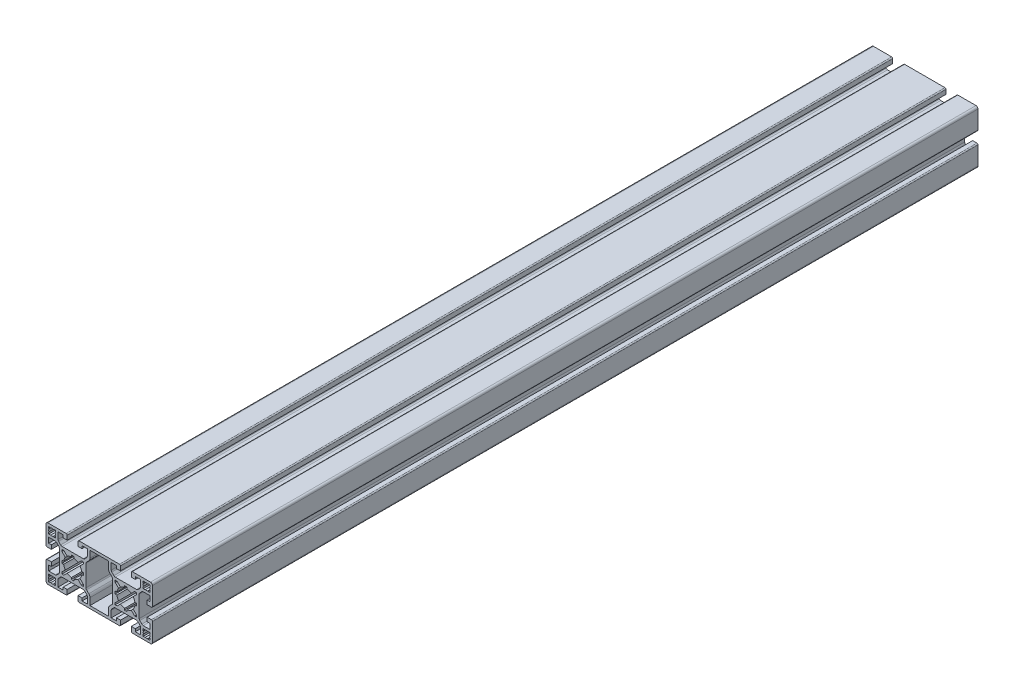
SolidWorks part; units mm, degrees
material "6063-T5"
ref_plane "Plano frontal" through (0, 0, 0) normal (0, 0, 1) x (1, 0, 0)
ref_plane "Plano superior" through (0, 0, 0) normal (0, 1, 0) x (1, 0, 0)
ref_plane "Plano direito" through (0, 0, 0) normal (1, 0, 0) x (0, 0, -1)
sketch "Esboço1" plane through (0, 0, 0) normal (0, 0, 1) x (1, 0, 0)
  line L0 (-33, 18) -> (-33, 16.5858)
  line L1 (-38.5, 20) -> (-24.85, 20)
  line L2 (-40, 18.5) -> (-40, 4.85)
  line L3 (-31, 18) -> (-27.05, 18)
  line L4 (-33, 18) -> (-34.4142, 18)
  line L5 (-30.5607, 11.9749) -> (-29.0251, 10.4393)
  line L6 (-27.9645, 10) -> (-12.0355, 10)
  line L7 (-34.4142, 18) -> (-34.5869, 17.8273)
  line L8 (-36.5858, 18) -> (-36.4131, 17.8273)
  line L9 (-33, 13) -> (-34.4142, 13)
  line L10 (-33, 13) -> (-33, 14.4142)
  line L11 (-36, 7.05) -> (-36, 4.05)
  line L12 (-33, 14.4142) -> (-33.1727, 14.5869)
  line L13 (-28, 6.5858) -> (-25.4989, 4.0847)
  line L14 (-21, 8) -> (-19, 8)
  line L15 (-21, 8) -> (-21, 6.7766)
  line L16 (-33, 16.5858) -> (-33.1727, 16.4131)
  line L17 (-28, 8) -> (-28, 6.5858)
  line L18 (-38, 13) -> (-38, 14.4142)
  line L19 (-38, 13) -> (-36.5858, 13)
  line L20 (-36.5858, 13) -> (-36.4131, 13.1727)
  line L21 (-34.4142, 13) -> (-34.5869, 13.1727)
  line L22 (-30, 7.9645) -> (-30, -7.9645)
  line L23 (-38, -11) -> (-38, -7.05)
  line L24 (-38, -14.4142) -> (-37.8273, -14.5869)
  line L25 (-7, 18) -> (-7, 12.8284)
  line L26 (-38, 18) -> (-36.5858, 18)
  line L27 (-38, 18) -> (-38, 16.5858)
  line L28 (-9.5607, 9.0251) -> (-7.8787, 10.7071)
  line L29 (-31.9749, -10.5607) -> (-30.4393, -9.0251)
  line L30 (-28, -1) -> (-26.7766, -1)
  line L31 (-9, -18) -> (-12.95, -18)
  line L32 (-24.05, 19.2) -> (-24.05, 16)
  line L33 (-9.4393, -11.9749) -> (-10.9749, -10.4393)
  line L34 (-38, 7.05) -> (-36, 7.05)
  line L35 (-19, -8) -> (-19, -6.7766)
  line L36 (-15.95, -19.2) -> (-15.95, -16)
  line L37 (-12.95, 16) -> (-15.95, 16)
  line L38 (-38, 11) -> (-33.0355, 11)
  line L39 (-31, 18) -> (-31, 13.0355)
  line L40 (-12, -6.5858) -> (-14.5011, -4.0847)
  line L41 (-13.4142, 8) -> (-15.9153, 5.4989)
  line L42 (-12, -8) -> (-12, -6.5858)
  line L43 (-12, 1) -> (-13.2234, 1)
  line L44 (-27.05, 18) -> (-27.05, 16)
  line L45 (-9, -18) -> (-9, -13.0355)
  line L46 (-28, 8) -> (-26.5858, 8)
  line L47 (-26.5858, 8) -> (-24.0847, 5.4989)
  line L48 (-27.05, 16) -> (-24.05, 16)
  line L49 (-12.95, -18) -> (-12.95, -16)
  line L50 (-38, -16.5858) -> (-37.8273, -16.4131)
  line L51 (-12, 8) -> (-13.4142, 8)
  line L52 (-39.2, -4.05) -> (-36, -4.05)
  line L53 (-12, -8) -> (-13.4142, -8)
  line L54 (-27.05, -16) -> (-24.05, -16)
  line L55 (-26.5858, -8) -> (-24.0847, -5.4989)
  line L56 (-28, -8) -> (-26.5858, -8)
  line L57 (-39.2, 4.05) -> (-36, 4.05)
  line L58 (-27.05, -18) -> (-27.05, -16)
  line L59 (-38, 16.5858) -> (-37.8273, 16.4131)
  line L60 (-12, -1) -> (-13.2234, -1)
  line L61 (-12.95, 18) -> (-12.95, 16)
  line L62 (-9, 18) -> (-9, 13.0355)
  line L63 (-13.4142, -8) -> (-15.9153, -5.4989)
  line L64 (-31, -18) -> (-31, -13.0355)
  line L65 (-12, 8) -> (-12, 6.5858)
  line L66 (-12, 6.5858) -> (-14.5011, 4.0847)
  line L67 (-38, -11) -> (-33.0355, -11)
  line L68 (-12.95, -16) -> (-15.95, -16)
  line L69 (-38, -7.05) -> (-36, -7.05)
  line L70 (-15.95, 19.2) -> (-15.95, 16)
  line L71 (-24.05, -19.2) -> (-24.05, -16)
  line L72 (-9.5607, -9.0251) -> (-7.8787, -10.7071)
  line L73 (-19, 8) -> (-19, 6.7766)
  line L74 (-38, -18) -> (-38, -16.5858)
  line L75 (-9.4393, 11.9749) -> (-10.9749, 10.4393)
  line L76 (-38, -18) -> (-36.5858, -18)
  line L77 (-9, 18) -> (-12.95, 18)
  line L78 (-7, -18) -> (-7, -12.8284)
  line L79 (-34.4142, -13) -> (-34.5869, -13.1727)
  line L80 (-36.5858, -13) -> (-36.4131, -13.1727)
  line L81 (-38, -13) -> (-36.5858, -13)
  line L82 (-38, -13) -> (-38, -14.4142)
  line L83 (-28, -8) -> (-28, -6.5858)
  line L84 (-33, -16.5858) -> (-33.1727, -16.4131)
  line L85 (-21, -8) -> (-21, -6.7766)
  line L86 (-21, -8) -> (-19, -8)
  line L87 (-28, -6.5858) -> (-25.4989, -4.0847)
  line L88 (-33, -14.4142) -> (-33.1727, -14.5869)
  line L89 (-36, -7.05) -> (-36, -4.05)
  line L90 (-33, -13) -> (-33, -14.4142)
  line L91 (-33, -13) -> (-34.4142, -13)
  line L92 (-36.5858, -18) -> (-36.4131, -17.8273)
  line L93 (-34.4142, -18) -> (-34.5869, -17.8273)
  line L94 (-27.9645, -10) -> (-12.0355, -10)
  line L95 (-30.5607, -11.9749) -> (-29.0251, -10.4393)
  line L96 (-33, -18) -> (-34.4142, -18)
  line L97 (-31, -18) -> (-27.05, -18)
  line L98 (-40, -18.5) -> (-40, -4.85)
  line L99 (-38.5, -20) -> (-24.85, -20)
  line L100 (-33, -18) -> (-33, -16.5858)
  line L101 (-28, 1) -> (-28, -1)
  line L102 (-12, -1) -> (-12, 1)
  line L103 (-10, 7.9645) -> (-10, -7.9645)
  line L104 (-15.15, 20) -> (15.15, 20)
  line L105 (-15.15, -20) -> (15.15, -20)
  line L108 (0, 25.8211) -> (0, -27.4656) construction
  line L109 (38, 11) -> (38, 7.05)
  line L110 (38, 14.4142) -> (37.8273, 14.5869)
  line L111 (-28, 1) -> (-26.7766, 1)
  line L112 (31.9749, 10.5607) -> (30.4393, 9.0251)
  line L113 (28, 1) -> (26.7766, 1)
  line L118 (10, 7.9645) -> (10, -7.9645)
  line L119 (12, -1) -> (12, 1)
  line L120 (-31.9749, 10.5607) -> (-30.4393, 9.0251)
  line L121 (28, 1) -> (28, -1)
  line L122 (33, -18) -> (33, -16.5858)
  line L123 (-38, 14.4142) -> (-37.8273, 14.5869)
  line L124 (38.5, -20) -> (24.85, -20)
  line L125 (40, -18.5) -> (40, -4.85)
  line L126 (31, -18) -> (27.05, -18)
  line L127 (33, -18) -> (34.4142, -18)
  line L128 (-38, 11) -> (-38, 7.05)
  line L129 (30.5607, -11.9749) -> (29.0251, -10.4393)
  line L130 (27.9645, -10) -> (12.0355, -10)
  line L131 (34.4142, -18) -> (34.5869, -17.8273)
  line L132 (36.5858, -18) -> (36.4131, -17.8273)
  line L133 (33, -13) -> (34.4142, -13)
  line L134 (33, -13) -> (33, -14.4142)
  line L135 (36, -7.05) -> (36, -4.05)
  line L136 (33, -14.4142) -> (33.1727, -14.5869)
  line L137 (28, -6.5858) -> (25.4989, -4.0847)
  line L138 (21, -8) -> (19, -8)
  line L139 (21, -8) -> (21, -6.7766)
  line L140 (33, -16.5858) -> (33.1727, -16.4131)
  line L141 (28, -8) -> (28, -6.5858)
  line L142 (38, -13) -> (38, -14.4142)
  line L143 (38, -13) -> (36.5858, -13)
  line L144 (36.5858, -13) -> (36.4131, -13.1727)
  line L145 (34.4142, -13) -> (34.5869, -13.1727)
  line L146 (7, -18) -> (7, -12.8284)
  line L147 (9, 18) -> (12.95, 18)
  line L148 (38, -18) -> (36.5858, -18)
  line L149 (9.4393, 11.9749) -> (10.9749, 10.4393)
  line L150 (38, -18) -> (38, -16.5858)
  line L151 (19, 8) -> (19, 6.7766)
  line L152 (9.5607, -9.0251) -> (7.8787, -10.7071)
  line L153 (24.05, -19.2) -> (24.05, -16)
  line L154 (15.95, 19.2) -> (15.95, 16)
  line L155 (38, -7.05) -> (36, -7.05)
  line L156 (12.95, -16) -> (15.95, -16)
  line L157 (38, -11) -> (33.0355, -11)
  line L158 (12, 6.5858) -> (14.5011, 4.0847)
  line L159 (12, 8) -> (12, 6.5858)
  line L160 (31, -18) -> (31, -13.0355)
  line L161 (13.4142, -8) -> (15.9153, -5.4989)
  line L162 (9, 18) -> (9, 13.0355)
  line L163 (12.95, 18) -> (12.95, 16)
  line L164 (12, -1) -> (13.2234, -1)
  line L165 (38, 16.5858) -> (37.8273, 16.4131)
  line L166 (27.05, -18) -> (27.05, -16)
  line L167 (39.2, 4.05) -> (36, 4.05)
  line L168 (28, -8) -> (26.5858, -8)
  line L169 (26.5858, -8) -> (24.0847, -5.4989)
  line L170 (27.05, -16) -> (24.05, -16)
  line L171 (12, -8) -> (13.4142, -8)
  line L172 (39.2, -4.05) -> (36, -4.05)
  line L173 (-1.5, 20) -> (-15.15, 20) [skipped]
  line L174 (0, 18.5) -> (0, 4.85) [skipped]
  line L175 (12, 8) -> (13.4142, 8)
  line L176 (0, -18.5) -> (0, -4.85) [skipped]
  line L177 (-0.8, 4.05) -> (-4, 4.05) [skipped]
  line L178 (-0.8, -4.05) -> (-4, -4.05) [skipped]
  line L179 (-1.5, -20) -> (-15.15, -20) [skipped]
  line L180 (38, -16.5858) -> (37.8273, -16.4131)
  line L181 (-2, 11) -> (-6.9645, 11) [skipped]
  line L182 (-7, 13) -> (-5.5858, 13) [skipped]
  line L183 (-7, 18) -> (-5.5858, 18) [skipped]
  line L184 (-2, 18) -> (-3.4142, 18) [skipped]
  line L185 (-2, 18) -> (-2, 16.5858) [skipped]
  line L186 (-2, 13) -> (-2, 14.4142) [skipped]
  line L187 (-2, 13) -> (-3.4142, 13) [skipped]
  line L188 (-2, 11) -> (-2, 7.05) [skipped]
  line L189 (-2, 7.05) -> (-4, 7.05) [skipped]
  line L190 (-4, 7.05) -> (-4, 4.05) [skipped]
  line L191 (-7, 13) -> (-7, 14.4142) [skipped]
  line L192 (-5.5858, 13) -> (-5.4131, 13.1727) [skipped]
  line L193 (-2, 14.4142) -> (-2.1727, 14.5869) [skipped]
  line L194 (-2, 16.5858) -> (-2.1727, 16.4131) [skipped]
  line L195 (-3.4142, 13) -> (-3.5869, 13.1727) [skipped]
  line L196 (-7, 14.4142) -> (-6.8273, 14.5869) [skipped]
  line L197 (-3.4142, 18) -> (-3.5869, 17.8273) [skipped]
  line L198 (-5.5858, 18) -> (-5.4131, 17.8273) [skipped]
  line L199 (-7, 18) -> (-7, 16.5858) [skipped]
  line L200 (-7, 16.5858) -> (-6.8273, 16.4131) [skipped]
  line L201 (-8.0251, 10.5607) -> (-9.5607, 9.0251) [skipped]
  line L202 (-8.0251, -10.5607) -> (-9.5607, -9.0251) [skipped]
  line L203 (-2, -11) -> (-6.9645, -11) [skipped]
  line L204 (-2, -11) -> (-2, -7.05) [skipped]
  line L205 (-2, -7.05) -> (-4, -7.05) [skipped]
  line L206 (-4, -7.05) -> (-4, -4.05) [skipped]
  line L207 (-7, -18) -> (-7, -16.5858) [skipped]
  line L208 (-7, -18) -> (-5.5858, -18) [skipped]
  line L209 (-5.5858, -18) -> (-5.4131, -17.8273) [skipped]
  line L210 (-3.4142, -18) -> (-3.5869, -17.8273) [skipped]
  line L211 (-7, -13) -> (-5.5858, -13) [skipped]
  line L212 (-7, -13) -> (-7, -14.4142) [skipped]
  line L213 (-7, -14.4142) -> (-6.8273, -14.5869) [skipped]
  line L214 (-7, -16.5858) -> (-6.8273, -16.4131) [skipped]
  line L215 (-2, -13) -> (-2, -14.4142) [skipped]
  line L216 (-2, -13) -> (-3.4142, -13) [skipped]
  line L217 (-3.4142, -13) -> (-3.5869, -13.1727) [skipped]
  line L218 (-5.5858, -13) -> (-5.4131, -13.1727) [skipped]
  line L219 (-2, -18) -> (-3.4142, -18) [skipped]
  line L220 (-2, -18) -> (-2, -16.5858) [skipped]
  line L221 (-2, -16.5858) -> (-2.1727, -16.4131) [skipped]
  line L222 (-2, -14.4142) -> (-2.1727, -14.5869) [skipped]
  line L223 (12.95, -18) -> (12.95, -16)
  line L224 (-40, -18.5) -> (-40, -4.85) [skipped]
  line L225 (27.05, 16) -> (24.05, 16)
  line L226 (26.5858, 8) -> (24.0847, 5.4989)
  line L227 (28, 8) -> (26.5858, 8)
  line L228 (9, -18) -> (9, -13.0355)
  line L229 (27.05, 18) -> (27.05, 16)
  line L230 (12, 1) -> (13.2234, 1)
  line L231 (12, -8) -> (12, -6.5858)
  line L232 (13.4142, 8) -> (15.9153, 5.4989)
  line L233 (12, -6.5858) -> (14.5011, -4.0847)
  line L234 (31, 18) -> (31, 13.0355)
  line L235 (38, 11) -> (33.0355, 11)
  line L236 (12.95, 16) -> (15.95, 16)
  line L237 (15.95, -19.2) -> (15.95, -16)
  line L238 (19, -8) -> (19, -6.7766)
  line L239 (38, 7.05) -> (36, 7.05)
  line L240 (9.4393, -11.9749) -> (10.9749, -10.4393)
  line L241 (24.05, 19.2) -> (24.05, 16)
  line L242 (9, -18) -> (12.95, -18)
  line L243 (28, -1) -> (26.7766, -1)
  line L244 (31.9749, -10.5607) -> (30.4393, -9.0251)
  line L245 (9.5607, 9.0251) -> (7.8787, 10.7071)
  line L246 (38, 18) -> (38, 16.5858)
  line L247 (38, 18) -> (36.5858, 18)
  line L248 (7, 18) -> (7, 12.8284)
  line L249 (38, -14.4142) -> (37.8273, -14.5869)
  line L250 (38, -11) -> (38, -7.05)
  line L251 (30, 7.9645) -> (30, -7.9645)
  line L252 (34.4142, 13) -> (34.5869, 13.1727)
  line L253 (36.5858, 13) -> (36.4131, 13.1727)
  line L254 (38, 13) -> (36.5858, 13)
  line L255 (38, 13) -> (38, 14.4142)
  line L256 (28, 8) -> (28, 6.5858)
  line L257 (33, 16.5858) -> (33.1727, 16.4131)
  line L258 (21, 8) -> (21, 6.7766)
  line L259 (21, 8) -> (19, 8)
  line L260 (28, 6.5858) -> (25.4989, 4.0847)
  line L261 (33, 14.4142) -> (33.1727, 14.5869)
  line L262 (36, 7.05) -> (36, 4.05)
  line L263 (33, 13) -> (33, 14.4142)
  line L264 (33, 13) -> (34.4142, 13)
  line L265 (36.5858, 18) -> (36.4131, 17.8273)
  line L266 (34.4142, 18) -> (34.5869, 17.8273)
  line L267 (27.9645, 10) -> (12.0355, 10)
  line L268 (30.5607, 11.9749) -> (29.0251, 10.4393)
  line L269 (33, 18) -> (34.4142, 18)
  line L270 (31, 18) -> (27.05, 18)
  line L271 (40, 18.5) -> (40, 4.85)
  line L272 (38.5, 20) -> (24.85, 20)
  line L273 (33, 18) -> (33, 16.5858)
  line L274 (-7, 18) -> (7, 18)
  line L275 (-7, -18) -> (7, -18)
  line L316 (-9, -18) -> (-12.95, -18) [skipped]
  line L317 (-9.4393, -11.9749) -> (-10.9749, -10.4393) [skipped]
  line L318 (-12, -6.5858) -> (-14.5011, -4.0847) [skipped]
  line L320 (-19, -8) -> (-19, -6.7766) [skipped]
  line L321 (-12, -8) -> (-12, -6.5858) [skipped]
  line L322 (-15.95, -19.2) -> (-15.95, -16) [skipped]
  line L323 (-9, -18) -> (-9, -13.0355) [skipped]
  line L324 (-12.95, -18) -> (-12.95, -16) [skipped]
  line L325 (-12, -8) -> (-13.4142, -8) [skipped]
  line L326 (-13.4142, -8) -> (-15.9153, -5.4989) [skipped]
  line L327 (-12.95, -16) -> (-15.95, -16) [skipped]
  line L329 (-12, -1) -> (-13.2234, -1) [skipped]
  line L330 (-38, -13) -> (-36.5858, -13) [skipped]
  line L331 (-38.5, -20) -> (-24.85, -20) [skipped]
  line L332 (-38, -11) -> (-38, -7.05) [skipped]
  line L333 (-38, -13) -> (-38, -14.4142) [skipped]
  line L334 (-31.9749, -10.5607) -> (-30.4393, -9.0251) [skipped]
  line L335 (-38, -14.4142) -> (-37.8273, -14.5869) [skipped]
  line L336 (-38, -16.5858) -> (-37.8273, -16.4131) [skipped]
  line L337 (-33, -13) -> (-33, -14.4142) [skipped]
  line L338 (-33, -13) -> (-34.4142, -13) [skipped]
  line L339 (-27.05, -16) -> (-24.05, -16) [skipped]
  line L340 (-34.4142, -13) -> (-34.5869, -13.1727) [skipped]
  line L341 (-26.5858, -8) -> (-24.0847, -5.4989) [skipped]
  line L342 (-28, -1) -> (-26.7766, -1) [skipped]
  line L343 (-36.5858, -13) -> (-36.4131, -13.1727) [skipped]
  line L344 (-28, -8) -> (-26.5858, -8) [skipped]
  line L345 (-33, -18) -> (-34.4142, -18) [skipped]
  line L346 (-33, -18) -> (-33, -16.5858) [skipped]
  line L347 (-33, -16.5858) -> (-33.1727, -16.4131) [skipped]
  line L348 (-33, -14.4142) -> (-33.1727, -14.5869) [skipped]
  line L349 (-38, -18) -> (-38, -16.5858) [skipped]
  line L350 (-38, -18) -> (-36.5858, -18) [skipped]
  line L351 (-39.2, -4.05) -> (-36, -4.05) [skipped]
  line L352 (-27.05, -18) -> (-27.05, -16) [skipped]
  line L353 (-31, -18) -> (-31, -13.0355) [skipped]
  line L354 (-38, -11) -> (-33.0355, -11) [skipped]
  line L355 (-38, -7.05) -> (-36, -7.05) [skipped]
  line L356 (-28, -8) -> (-28, -6.5858) [skipped]
  line L357 (-28, -6.5858) -> (-25.4989, -4.0847) [skipped]
  line L358 (-36, -7.05) -> (-36, -4.05) [skipped]
  line L359 (-24.05, -19.2) -> (-24.05, -16) [skipped]
  line L360 (-36.5858, -18) -> (-36.4131, -17.8273) [skipped]
  line L361 (-21, -8) -> (-21, -6.7766) [skipped]
  line L362 (-30.5607, -11.9749) -> (-29.0251, -10.4393) [skipped]
  line L363 (-34.4142, -18) -> (-34.5869, -17.8273) [skipped]
  line L364 (-31, -18) -> (-27.05, -18) [skipped]
  arc A0 (-30.5607, 11.9749) -> (-31, 13.0355) centre (-29.5, 13.0355) cw
  arc A1 (-37.8273, 16.4131) -> (-37.8273, 14.5869) centre (-35.5, 15.5) ccw
  arc A2 (-38.5, 20) -> (-40, 18.5) centre (-38.5, 18.5) ccw
  arc A3 (-25.4989, 4.0847) -> (-26.7766, 1) centre (-20, 0) ccw
  arc A4 (-31.9749, 10.5607) -> (-33.0355, 11) centre (-33.0355, 9.5) ccw
  arc A5 (-30, 7.9645) -> (-30.4393, 9.0251) centre (-31.5, 7.9645) ccw
  arc A6 (-40, 4.85) -> (-39.2, 4.05) centre (-39.2, 4.85) ccw
  arc A7 (-24.0847, 5.4989) -> (-21, 6.7766) centre (-20, 0) cw
  arc A8 (-34.5869, 17.8273) -> (-36.4131, 17.8273) centre (-35.5, 15.5) ccw
  arc A9 (-33.1727, 14.5869) -> (-33.1727, 16.4131) centre (-35.5, 15.5) ccw
  arc A10 (-36.4131, 13.1727) -> (-34.5869, 13.1727) centre (-35.5, 15.5) ccw
  arc A11 (-7, 12.8284) -> (-7.8787, 10.7071) centre (-10, 12.8284) cw
  arc A12 (-10, -7.9645) -> (-9.5607, -9.0251) centre (-8.5, -7.9645) ccw
  arc A13 (-14.5011, -4.0847) -> (-13.2234, -1) centre (-20, 0) ccw
  arc A14 (-15.9153, 5.4989) -> (-19, 6.7766) centre (-20, 0) ccw
  arc A15 (-9.4393, 11.9749) -> (-9, 13.0355) centre (-10.5, 13.0355) ccw
  arc A16 (-12.0355, 10) -> (-10.9749, 10.4393) centre (-12.0355, 11.5) ccw
  arc A17 (-24.85, 20) -> (-24.05, 19.2) centre (-24.85, 19.2) cw
  arc A18 (-27.9645, 10) -> (-29.0251, 10.4393) centre (-27.9645, 11.5) cw
  arc A19 (-15.15, -20) -> (-15.95, -19.2) centre (-15.15, -19.2) cw
  arc A20 (-27.9645, -10) -> (-29.0251, -10.4393) centre (-27.9645, -11.5) ccw
  arc A21 (-15.15, 20) -> (-15.95, 19.2) centre (-15.15, 19.2) ccw
  arc A22 (-14.5011, 4.0847) -> (-13.2234, 1) centre (-20, 0) cw
  arc A23 (-24.85, -20) -> (-24.05, -19.2) centre (-24.85, -19.2) ccw
  arc A24 (-12.0355, -10) -> (-10.9749, -10.4393) centre (-12.0355, -11.5) cw
  arc A25 (-9.4393, -11.9749) -> (-9, -13.0355) centre (-10.5, -13.0355) cw
  arc A26 (-15.9153, -5.4989) -> (-19, -6.7766) centre (-20, 0) cw
  arc A27 (-10, 7.9645) -> (-9.5607, 9.0251) centre (-8.5, 7.9645) cw
  arc A28 (-7, -12.8284) -> (-7.8787, -10.7071) centre (-10, -12.8284) ccw
  arc A29 (-36.4131, -13.1727) -> (-34.5869, -13.1727) centre (-35.5, -15.5) cw
  arc A30 (-33.1727, -14.5869) -> (-33.1727, -16.4131) centre (-35.5, -15.5) cw
  arc A31 (-34.5869, -17.8273) -> (-36.4131, -17.8273) centre (-35.5, -15.5) cw
  arc A32 (-24.0847, -5.4989) -> (-21, -6.7766) centre (-20, 0) ccw
  arc A33 (-40, -4.85) -> (-39.2, -4.05) centre (-39.2, -4.85) cw
  arc A34 (-30, -7.9645) -> (-30.4393, -9.0251) centre (-31.5, -7.9645) cw
  arc A35 (-31.9749, -10.5607) -> (-33.0355, -11) centre (-33.0355, -9.5) cw
  arc A36 (-25.4989, -4.0847) -> (-26.7766, -1) centre (-20, 0) cw
  arc A37 (-38.5, -20) -> (-40, -18.5) centre (-38.5, -18.5) cw
  arc A38 (-37.8273, -16.4131) -> (-37.8273, -14.5869) centre (-35.5, -15.5) cw
  arc A39 (-30.5607, -11.9749) -> (-31, -13.0355) centre (-29.5, -13.0355) ccw
  arc A40 (30.5607, -11.9749) -> (31, -13.0355) centre (29.5, -13.0355) cw
  arc A41 (37.8273, -16.4131) -> (37.8273, -14.5869) centre (35.5, -15.5) ccw
  arc A42 (38.5, -20) -> (40, -18.5) centre (38.5, -18.5) ccw
  arc A43 (25.4989, -4.0847) -> (26.7766, -1) centre (20, 0) ccw
  arc A44 (31.9749, -10.5607) -> (33.0355, -11) centre (33.0355, -9.5) ccw
  arc A45 (30, -7.9645) -> (30.4393, -9.0251) centre (31.5, -7.9645) ccw
  arc A46 (40, -4.85) -> (39.2, -4.05) centre (39.2, -4.85) ccw
  arc A47 (24.0847, -5.4989) -> (21, -6.7766) centre (20, 0) cw
  arc A48 (34.5869, -17.8273) -> (36.4131, -17.8273) centre (35.5, -15.5) ccw
  arc A49 (33.1727, -14.5869) -> (33.1727, -16.4131) centre (35.5, -15.5) ccw
  arc A50 (36.4131, -13.1727) -> (34.5869, -13.1727) centre (35.5, -15.5) ccw
  arc A51 (7, -12.8284) -> (7.8787, -10.7071) centre (10, -12.8284) cw
  arc A52 (10, 7.9645) -> (9.5607, 9.0251) centre (8.5, 7.9645) ccw
  arc A53 (15.9153, -5.4989) -> (19, -6.7766) centre (20, 0) ccw
  arc A54 (0, 18.5) -> (-1.5, 20) centre (-1.5, 18.5) ccw [skipped]
  arc A55 (-1.5, -20) -> (0, -18.5) centre (-1.5, -18.5) ccw [skipped]
  arc A56 (0, -4.85) -> (-0.8, -4.05) centre (-0.8, -4.85) ccw [skipped]
  arc A57 (0, 4.85) -> (-0.8, 4.05) centre (-0.8, 4.85) cw [skipped]
  arc A58 (-3.5869, 17.8273) -> (-5.4131, 17.8273) centre (-4.5, 15.5) ccw [skipped]
  arc A59 (-2.1727, 14.5869) -> (-2.1727, 16.4131) centre (-4.5, 15.5) ccw [skipped]
  arc A60 (-5.4131, 13.1727) -> (-3.5869, 13.1727) centre (-4.5, 15.5) ccw [skipped]
  arc A61 (-8.0251, 10.5607) -> (-6.9645, 11) centre (-6.9645, 9.5) cw [skipped]
  arc A62 (-6.8273, 16.4131) -> (-6.8273, 14.5869) centre (-4.5, 15.5) ccw [skipped]
  arc A63 (-8.0251, -10.5607) -> (-6.9645, -11) centre (-6.9645, -9.5) ccw [skipped]
  arc A64 (-2.1727, -16.4131) -> (-2.1727, -14.5869) centre (-4.5, -15.5) ccw [skipped]
  arc A65 (-5.4131, -17.8273) -> (-3.5869, -17.8273) centre (-4.5, -15.5) ccw [skipped]
  arc A66 (-6.8273, -14.5869) -> (-6.8273, -16.4131) centre (-4.5, -15.5) ccw [skipped]
  arc A67 (-3.5869, -13.1727) -> (-5.4131, -13.1727) centre (-4.5, -15.5) ccw [skipped]
  arc A68 (9.4393, -11.9749) -> (9, -13.0355) centre (10.5, -13.0355) ccw
  arc A69 (12.0355, -10) -> (10.9749, -10.4393) centre (12.0355, -11.5) ccw
  arc A70 (24.85, -20) -> (24.05, -19.2) centre (24.85, -19.2) cw
  arc A71 (14.5011, 4.0847) -> (13.2234, 1) centre (20, 0) ccw
  arc A72 (15.15, 20) -> (15.95, 19.2) centre (15.15, 19.2) cw
  arc A73 (27.9645, -10) -> (29.0251, -10.4393) centre (27.9645, -11.5) cw
  arc A74 (15.15, -20) -> (15.95, -19.2) centre (15.15, -19.2) ccw
  arc A75 (27.9645, 10) -> (29.0251, 10.4393) centre (27.9645, 11.5) ccw
  arc A76 (24.85, 20) -> (24.05, 19.2) centre (24.85, 19.2) ccw
  arc A77 (12.0355, 10) -> (10.9749, 10.4393) centre (12.0355, 11.5) cw
  arc A78 (9.4393, 11.9749) -> (9, 13.0355) centre (10.5, 13.0355) cw
  arc A79 (15.9153, 5.4989) -> (19, 6.7766) centre (20, 0) cw
  arc A80 (14.5011, -4.0847) -> (13.2234, -1) centre (20, 0) cw
  arc A81 (10, -7.9645) -> (9.5607, -9.0251) centre (8.5, -7.9645) cw
  arc A82 (7, 12.8284) -> (7.8787, 10.7071) centre (10, 12.8284) ccw
  arc A83 (36.4131, 13.1727) -> (34.5869, 13.1727) centre (35.5, 15.5) cw
  arc A84 (33.1727, 14.5869) -> (33.1727, 16.4131) centre (35.5, 15.5) cw
  arc A85 (34.5869, 17.8273) -> (36.4131, 17.8273) centre (35.5, 15.5) cw
  arc A86 (24.0847, 5.4989) -> (21, 6.7766) centre (20, 0) ccw
  arc A87 (40, 4.85) -> (39.2, 4.05) centre (39.2, 4.85) cw
  arc A88 (30, 7.9645) -> (30.4393, 9.0251) centre (31.5, 7.9645) cw
  arc A89 (31.9749, 10.5607) -> (33.0355, 11) centre (33.0355, 9.5) cw
  arc A90 (25.4989, 4.0847) -> (26.7766, 1) centre (20, 0) cw
  arc A91 (38.5, 20) -> (40, 18.5) centre (38.5, 18.5) cw
  arc A92 (37.8273, 16.4131) -> (37.8273, 14.5869) centre (35.5, 15.5) cw
  arc A93 (30.5607, 11.9749) -> (31, 13.0355) centre (29.5, 13.0355) ccw
  arc A96 (-9.4393, -11.9749) -> (-9, -13.0355) centre (-10.5, -13.0355) cw [skipped]
  arc A97 (-14.5011, -4.0847) -> (-13.2234, -1) centre (-20, 0) ccw [skipped]
  arc A98 (-10, -7.9645) -> (-9.5607, -9.0251) centre (-8.5, -7.9645) ccw [skipped]
  arc A99 (-15.9153, -5.4989) -> (-19, -6.7766) centre (-20, 0) cw [skipped]
  arc A100 (-15.15, -20) -> (-15.95, -19.2) centre (-15.15, -19.2) cw [skipped]
  arc A101 (-12.0355, -10) -> (-10.9749, -10.4393) centre (-12.0355, -11.5) cw [skipped]
  arc A102 (-31.9749, -10.5607) -> (-33.0355, -11) centre (-33.0355, -9.5) cw [skipped]
  arc A103 (-36.4131, -17.8273) -> (-34.5869, -17.8273) centre (-35.5, -15.5) ccw [skipped]
  arc A104 (-40, -18.5) -> (-38.5, -20) centre (-38.5, -18.5) ccw [skipped]
  arc A105 (-24.0847, -5.4989) -> (-21, -6.7766) centre (-20, 0) ccw [skipped]
  arc A106 (-30.5607, -11.9749) -> (-31, -13.0355) centre (-29.5, -13.0355) ccw [skipped]
  arc A107 (-27.9645, -10) -> (-29.0251, -10.4393) centre (-27.9645, -11.5) ccw [skipped]
  arc A108 (-24.85, -20) -> (-24.05, -19.2) centre (-24.85, -19.2) ccw [skipped]
  arc A109 (-25.4989, -4.0847) -> (-26.7766, -1) centre (-20, 0) cw [skipped]
  arc A110 (-37.8273, -14.5869) -> (-37.8273, -16.4131) centre (-35.5, -15.5) ccw [skipped]
  arc A111 (-34.5869, -13.1727) -> (-36.4131, -13.1727) centre (-35.5, -15.5) ccw [skipped]
  arc A112 (-33.1727, -16.4131) -> (-33.1727, -14.5869) centre (-35.5, -15.5) ccw [skipped]
  arc A113 (-40, -4.85) -> (-39.2, -4.05) centre (-39.2, -4.85) cw [skipped]
  arc A114 (-30, -7.9645) -> (-30.4393, -9.0251) centre (-31.5, -7.9645) cw [skipped]
  point P5 (-4.5, 15.5)
  point P7 (-35.5, -15.5)
  point P20 (-20, 0)
  point P31 (-4.5, 15.5)
  point P38 (-20, 0)
  point P45 (-35.5, 15.5)
  point P57 (-4.5, -15.5)
  point P66 (-4.5, -15.5)
  point P77 (-35.5, -15.5)
  point P79 (-20, 0)
  point P80 (-20, 0)
  point P81 (-20, 0)
  point P207 (-35.5, 15.5)
  dimension "D2" = 4
  dimension "D1" = 4
extrude "Ressalto-extrusão1" add sketch "Esboço1" along normal mid plane 620
sketch "Sketch1" plane through (0, 20, 0) normal (0, 1, 0) x (1, 0, 0)
  line L0 (0, 270) -> (0, -270)
  line L2 (0, 0) -> (15.15, 0) construction
  line L3 (19.7716, 296.5) -> (-19.7716, 296.5)
  line L4 (19.7716, 296.5) -> (19.7716, 243.5)
  line L5 (19.7716, 243.5) -> (-19.7716, 243.5)
  line L6 (-19.7716, 296.5) -> (-19.7716, 243.5)
  line L7 (19.7716, 296.5) -> (-19.7716, 243.5) construction
  line L8 (19.7716, 243.5) -> (-19.7716, 296.5) construction
  line L9 (15.15, -310) -> (15.15, 310) construction
  line L10 (19.7716, -243.5) -> (-19.7716, -243.5)
  line L11 (-19.7716, -296.5) -> (-19.7716, -243.5)
  line L12 (19.7716, -296.5) -> (-19.7716, -296.5)
  line L13 (19.7716, -296.5) -> (19.7716, -243.5)
  circle A0 centre (19.7716, 296.5) radius 3
  circle A1 centre (19.7716, 243.5) radius 3
  circle A2 centre (-19.7716, 243.5) radius 3
  circle A3 centre (-19.7716, 296.5) radius 3
  circle A4 centre (19.7716, -243.5) radius 3
  circle A5 centre (-19.7716, -243.5) radius 3
  circle A6 centre (-19.7716, -296.5) radius 3
  circle A7 centre (19.7716, -296.5) radius 3
  point P4 (0, 0)
  point P6 (0, 0)
  dimension "D4" = 6
  dimension "D1" = 540
  dimension "D2" = 53
  dimension "D3" = 39.5432
extrude "Cut-Extrude1" cut sketch "Sketch1" against normal through all contours L4 A0 L3 | L3 A0 L4 | L4 A1 L5 | L5 A1 L4 | L3 A3 L6 | L6 A3 L3 | L5 A2 L6 | L6 A2 L5 | A4 L10 L13 | A4 L13 L10 | A7 L12 L13 | A7 L13 L12 | A5 L11 L10 | A5 L10 L11 | A6 L12 L11 | A6 L11 L12 region at (18.4984, 20, -244.7732) region at (20.196, 20, -243.0756) region at (-20.196, 20, -243.0756) region at (-18.4984, 20, -244.7732) region at (20.196, 20, 243.0756) region at (18.4984, 20, 244.7732) region at (-18.4984, 20, 244.7732) region at (-20.196, 20, 243.0756) region at (18.4984, 20, -295.2268) region at (20.196, 20, -296.9244) region at (-20.196, 20, -296.9244) region at (-18.4984, 20, -295.2268) region at (20.196, 20, 296.9244) region at (18.4984, 20, 295.2268) region at (-18.4984, 20, 295.2268) region at (-20.196, 20, 296.9244)
